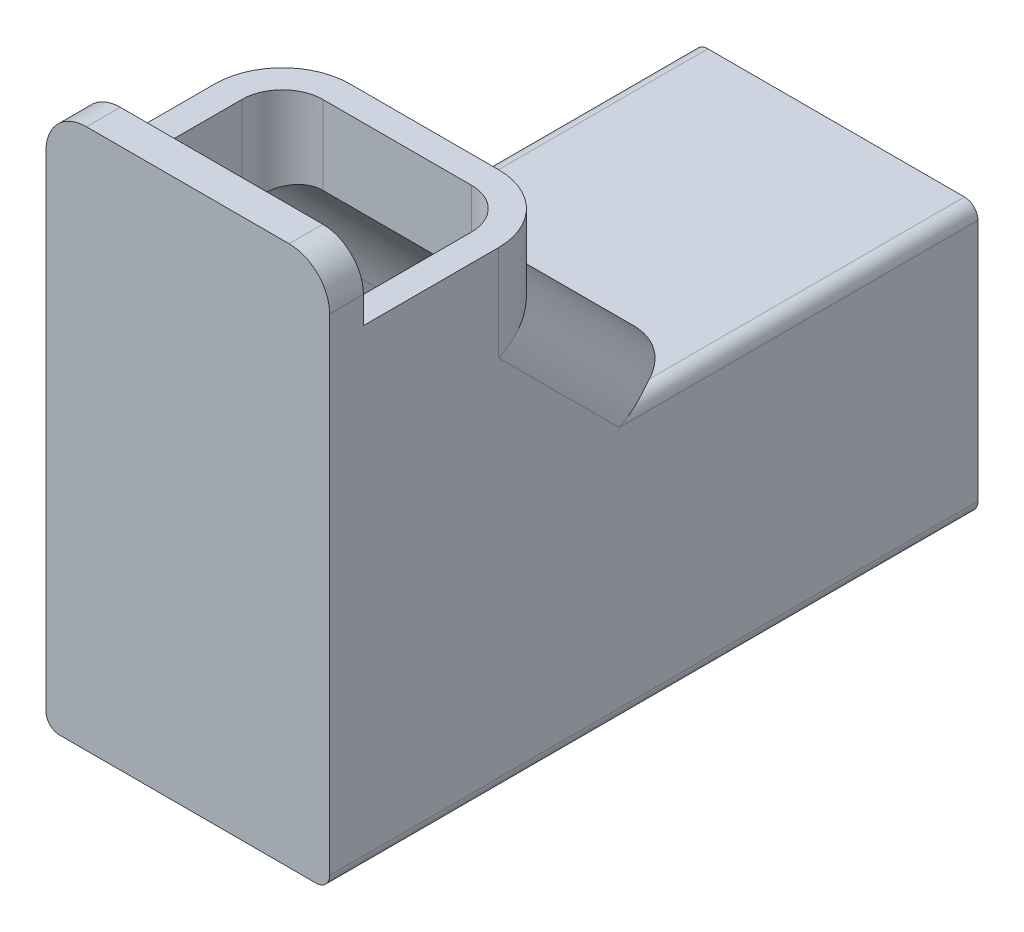
SolidWorks part; units mm, degrees
ref_plane "Alzado" through (0, 0, 0) normal (0, 0, 1) x (1, 0, 0)
ref_plane "Planta" through (0, 0, 0) normal (0, 1, 0) x (1, 0, 0)
ref_plane "Vista lateral" through (0, 0, 0) normal (1, 0, 0) x (0, 0, -1)
sketch "Croquis1" plane through (0, 0, 0) normal (1, 0, 0) x (0, 0, -1)
  line L0 (0, 0) -> (0, 40)
  line L1 (0, 40) -> (2.5, 40)
  line L2 (2.5, 40) -> (2.5, 35)
  line L3 (2.5, 35) -> (17.5, 35)
  line L4 (17.5, 35) -> (17.5, 30)
  line L5 (17.5, 30) -> (27.5, 20)
  line L6 (27.5, 20) -> (48, 20)
  line L7 (48, 20) -> (48, 0)
  line L8 (48, 0) -> (0, 0)
  dimension "D1" = 48
  dimension "D2" = 20
  dimension "D3" = 40
  dimension "D4" = 5
  dimension "D5" = 2.5
  dimension "D6" = 15
  dimension "D7" = 5
  dimension "D8" = 135
extrude "Saliente-Extruir1" add sketch "Croquis1" along normal blind 21
fillet "Redondeo1" radius 1 4 edges at (0, 0, -24) (21, 0, -24) (0, 20, -37.75) (21, 20, -37.75)
fillet "Redondeo2" radius 5 2 edges at (0, 32.5, -17.5) (21, 32.5, -17.5)
fillet "Redondeo3" radius 5 2 edges at (0, 27, -20.5) (21, 27, -20.5)
fillet "Redondeo4" radius 3 2 edges at (0, 40, -1.25) (21, 40, -1.25)
shell "Vaciado1" thickness 2 removed face at (10.5, 10, -48) removed face at (10.5, 35, -11.1785)
